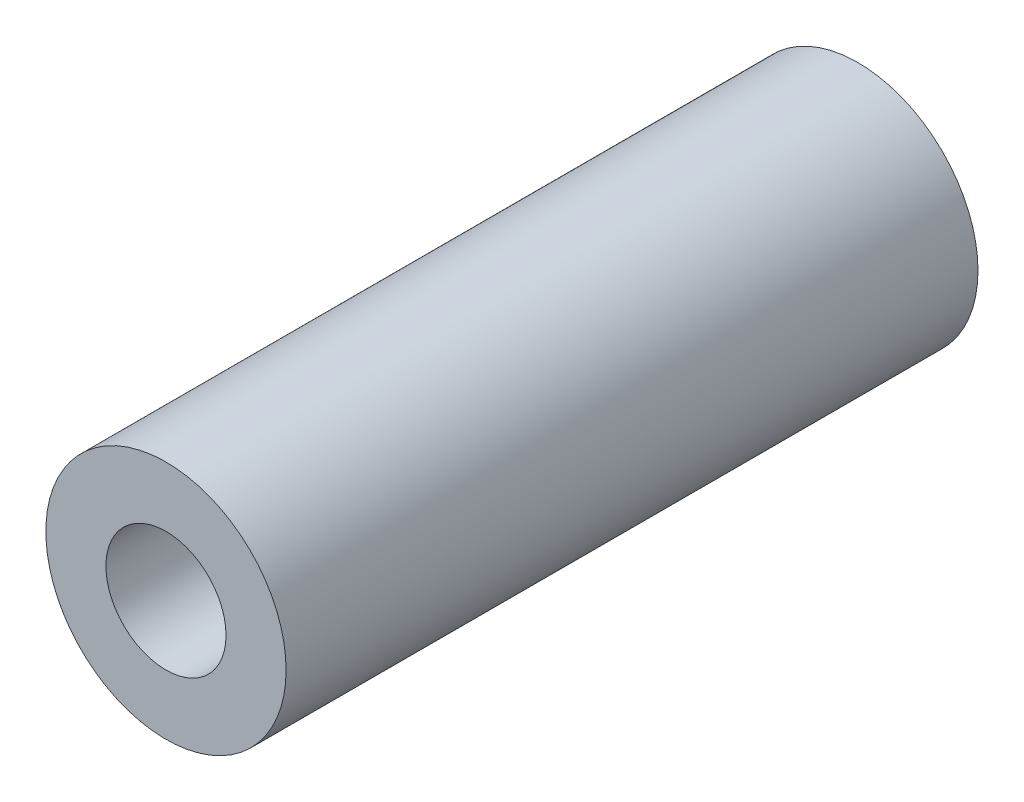
SolidWorks part; units mm, degrees
material "ABS"
ref_plane "Front Plane" through (0, 0, 0) normal (0, 0, 1) x (1, 0, 0)
ref_plane "Top Plane" through (0, 0, 0) normal (0, 1, 0) x (1, 0, 0)
ref_plane "Right Plane" through (0, 0, 0) normal (1, 0, 0) x (0, 0, -1)
sketch "Sketch1" plane through (0, 0, 0) normal (0, 0, 1) x (1, 0, 0)
  circle A0 centre (0, 0) radius 1.5875
  circle A1 centre (0, 0) radius 3.175
  dimension "D1" = 3.175
  dimension "D2" = 6.35
extrude "Boss-Extrude2" add sketch "Sketch1" along normal blind 18.288 contours A1 | A0
